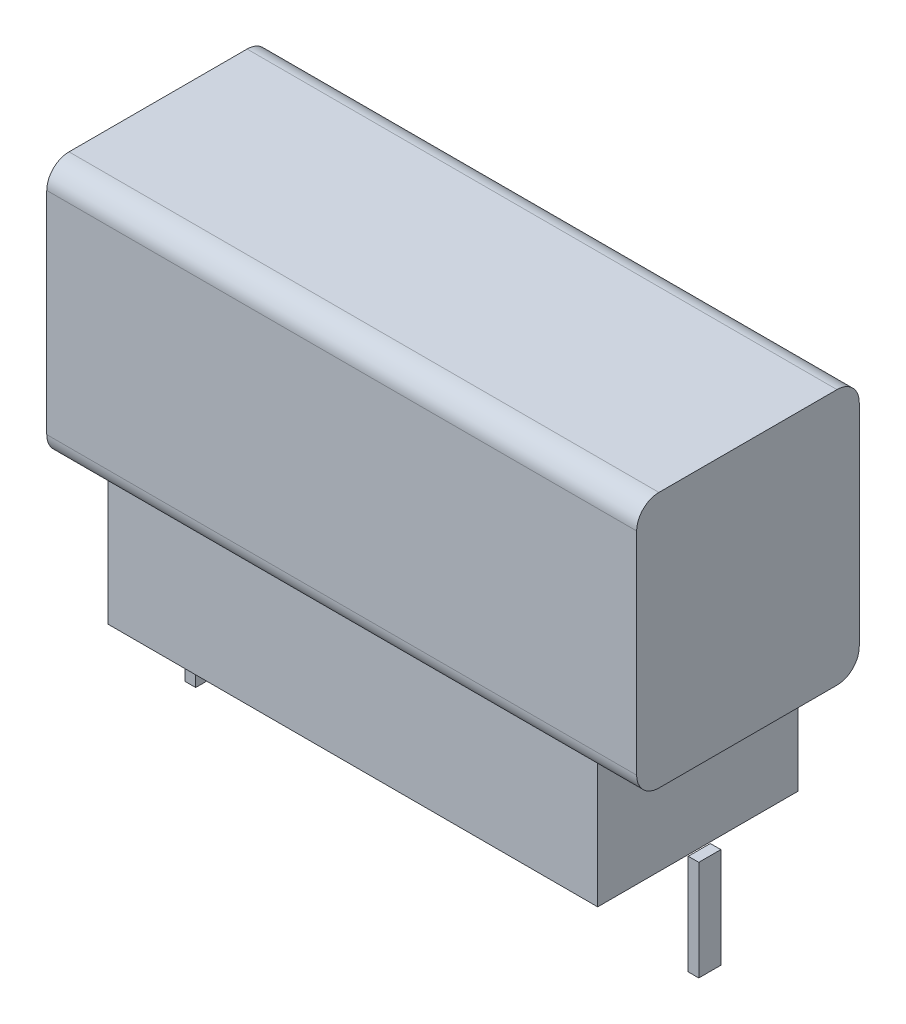
SolidWorks part; units mm, degrees
ref_plane "前视" through (0, 0, 0) normal (0, 0, 1) x (1, 0, 0)
ref_plane "上视" through (0, 0, 0) normal (0, 1, 0) x (1, 0, 0)
ref_plane "右视" through (0, 0, 0) normal (1, 0, 0) x (0, 0, -1)
sketch "草图1" plane through (0, 0, 0) normal (0, 1, 0) x (1, 0, 0)
  line L0 (-28.3755, 0) -> (18.4931, 0) construction
  line L1 (-11, 4.5) -> (11, 4.5)
  line L2 (-11, 4.5) -> (-11, -4.5)
  line L3 (-11, -4.5) -> (11, -4.5)
  line L4 (11, 4.5) -> (11, -4.5)
  line L5 (0, 15.354) -> (0, -11.4281) construction
  dimension "D1" = 22
  dimension "D2" = 9
extrude "凸台-拉伸1" add sketch "草图1" along normal blind 5.5
sketch "草图2" plane through (0, 5.5, 0) normal (0, 1, 0) x (1, 0, 0)
  line L0 (0, 12.4393) -> (0, -11.6854) construction
  line L1 (-13.25, 5) -> (13.25, 5)
  line L2 (-13.25, 5) -> (-13.25, -5)
  line L3 (-13.25, -5) -> (13.25, -5)
  line L4 (13.25, 5) -> (13.25, -5)
  line L5 (-22.6876, 0) -> (17.269, 0) construction
  dimension "D1" = 26.5
  dimension "D2" = 10
extrude "凸台-拉伸2" add sketch "草图2" along normal offset from surface (11.5 mm away) 17 up to face at (0, 0, 0)
sketch "草图3" plane through (0, 0, 0) normal (0, -1, 0) x (1, 0, 0)
  line L0 (-19.2933, 0) -> (16.6525, 0) construction
  line L1 (0, 2.0844) -> (0, -2.2363) construction
  line L2 (-11.0634, 0.4958) -> (-11.5366, 0.4958)
  line L3 (-11.0634, 0.4958) -> (-11.0634, -0.4958)
  line L4 (-11.0634, -0.4958) -> (-11.5366, -0.4958)
  line L5 (-11.5366, 0.4958) -> (-11.5366, -0.4958)
  line L6 (11.3, 1.4564) -> (11.3, -1.9235) construction
  line L7 (11.5366, 0.4958) -> (11.5366, -0.4958)
  line L8 (11.0634, -0.4958) -> (11.5366, -0.4958)
  line L9 (11.0634, 0.4958) -> (11.0634, -0.4958)
  line L10 (-11.3, 1.4564) -> (-11.3, -1.9235) construction
  line L11 (11.0634, 0.4958) -> (11.5366, 0.4958)
  dimension "D1" = 22.6
extrude "凸台-拉伸3" add sketch "草图3" along normal blind 4.5 separate body
fillet "圆角1" radius 1 4 edges at (0, 5.5, 5) (0, 5.5, -5) (0, 17, -5) (0, 17, 5)
